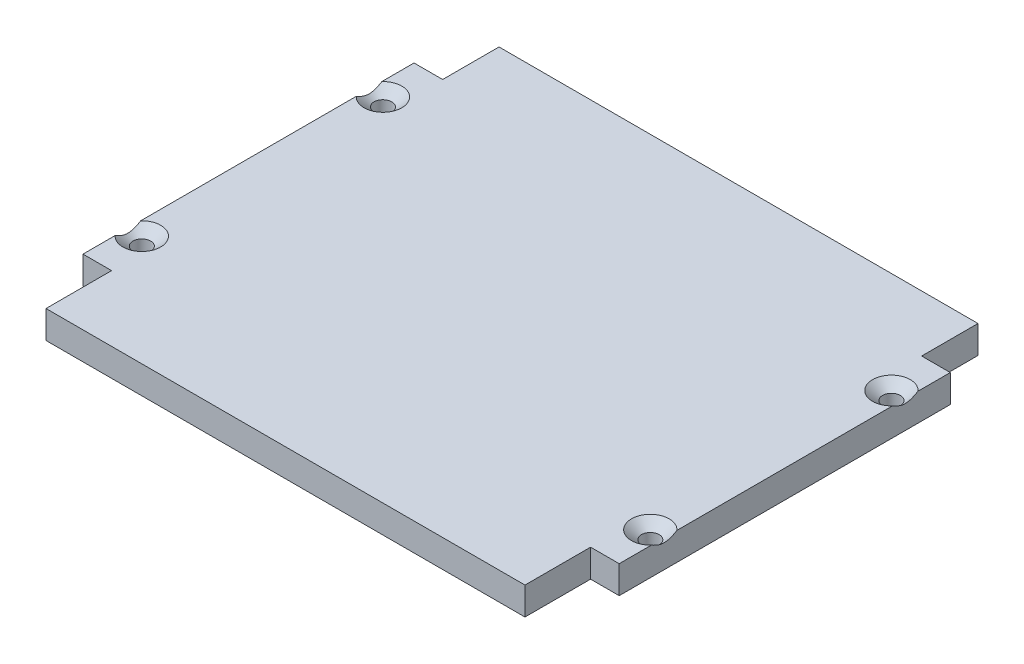
SolidWorks part; units mm, degrees
ref_plane "Front Plane" through (0, 0, 0) normal (0, 0, 1) x (1, 0, 0)
ref_plane "Top Plane" through (0, 0, 0) normal (0, 1, 0) x (1, 0, 0)
ref_plane "Right Plane" through (0, 0, 0) normal (1, 0, 0) x (0, 0, -1)
sketch "Sketch1" plane through (0, 0, 0) normal (0, 1, 0) x (1, 0, 0)
  line L0 (-41.1226, 38.1) -> (41.1226, 38.1)
  line L1 (41.1226, 38.1) -> (41.1226, 28.4226)
  line L2 (41.1226, 28.4226) -> (46.0375, 28.4226)
  line L3 (46.0375, 28.4226) -> (46.0375, -28.4226)
  line L4 (46.0375, -28.4226) -> (41.1226, -28.4226)
  line L5 (41.1226, -28.4226) -> (41.1226, -39.6875)
  line L6 (41.1226, -39.6875) -> (-41.1226, -39.6875)
  line L7 (0, -1000) -> (0, 49000) construction
  line L8 (-41.1226, -28.4226) -> (-41.1226, -39.6875)
  line L9 (-46.0375, -28.4226) -> (-41.1226, -28.4226)
  line L10 (-46.0375, 28.4226) -> (-46.0375, -28.4226)
  line L11 (-41.1226, 28.4226) -> (-46.0375, 28.4226)
  line L12 (-41.1226, 38.1) -> (-41.1226, 28.4226)
  circle A0 centre (43.6562, 20.701) radius 1.524
  circle A1 centre (43.6562, -20.701) radius 1.524
  circle A2 centre (-43.6562, -20.701) radius 1.524
  circle A3 centre (-43.6562, 20.701) radius 1.524
  point P9 (46.0375, 0)
  point P21 (0, -39.6875)
  point P26 (0, 38.1)
  dimension "D6" = 3.048
  dimension "D1" = 4.9149
  dimension "D2" = 9.6774
  dimension "D3" = 77.7875
  dimension "D4" = 7.7216
  dimension "D5" = 7.7216
  dimension "D7" = 2.3813
  dimension "D8" = 92.075
  dimension "D9" = 56.8452
extrude "Boss-Extrude1" add sketch "Sketch1" along normal blind 4.7625
chamfer "Chamfer1" distance 1.7145 angle 41 4 edges at (43.6562, 4.7625, -19.177) (43.6562, 4.7625, 22.225) (-43.6562, 4.7625, -22.225) (-43.6562, 4.7625, 19.177) first distance on face at (-43.6562, 4.7625, 19.177)
